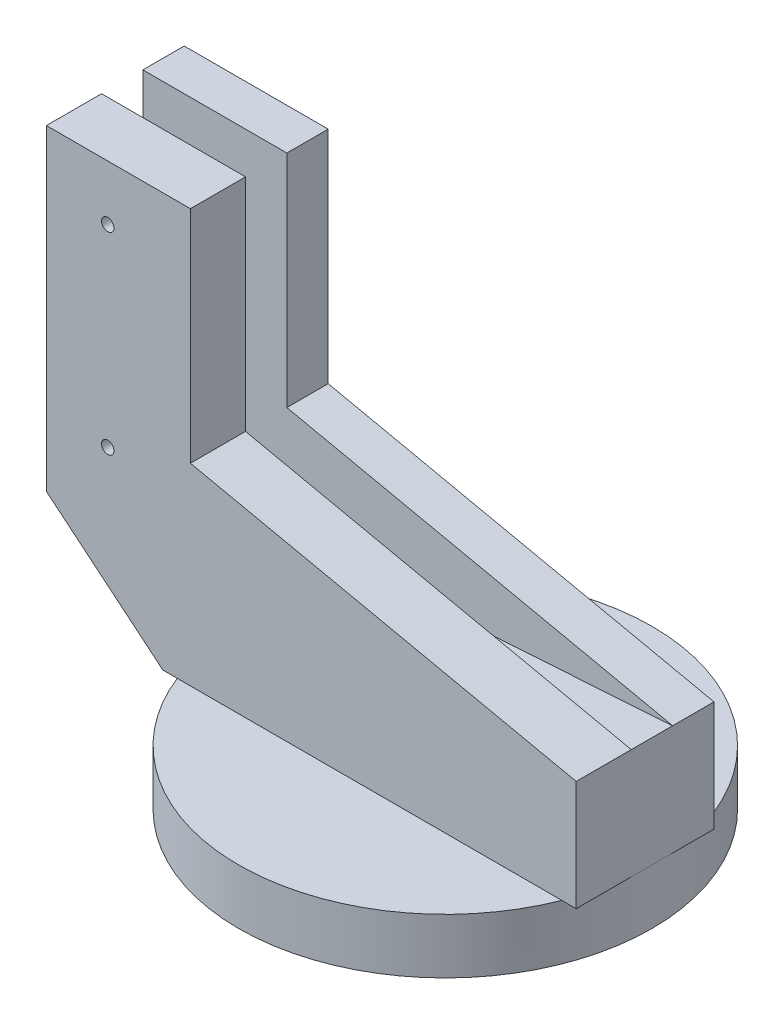
SolidWorks part; units mm, degrees
ref_plane "Front Plane" through (0, 0, 0) normal (0, 0, 1) x (1, 0, 0)
ref_plane "Top Plane" through (0, 0, 0) normal (0, 1, 0) x (1, 0, 0)
ref_plane "Right Plane" through (0, 0, 0) normal (1, 0, 0) x (0, 0, -1)
sketch "Sketch1" plane through (0, 0, 0) normal (0, 1, 0) x (1, 0, 0)
  circle A0 centre (0, 0) radius 75
  dimension "D1" = 150
extrude "Boss-Extrude1" add sketch "Sketch1" along normal blind 20
sketch "Sketch2" plane through (0, 0, 0) normal (0, 0, 1) x (1, 0, 0)
  line L0 (75, 20) -> (-75, 20) construction
  line L1 (75, 20) -> (-75, 20)
  line L2 (-95, 150) -> (-95, 80) construction
  line L3 (-75, 20) -> (-117.25, 55)
  line L4 (-117.25, 55) -> (-117.25, 170)
  line L5 (-117.25, 170) -> (-65, 170)
  line L6 (-65, 170) -> (-65, 90)
  line L7 (-65, 90) -> (75, 60)
  line L8 (75, 60) -> (75, 20)
  line L9 (-117.25, 55) -> (0, 55)
  line L10 (0, 55) -> (75, 60)
  circle A0 centre (-95, 150) radius 2.25
  circle A1 centre (-95, 80) radius 2.25
  dimension "D1" = 4.5
  dimension "D2" = 4.5
  dimension "D4" = 30
  dimension "D8" = 20
  dimension "D3" = 70
  dimension "D5" = 20
  dimension "D6" = 140
  dimension "D7" = 150
  dimension "D9" = 115
  dimension "D10" = 80
  dimension "D11" = 40
  dimension "D12" = 75
extrude "Boss-Extrude2" add sketch "Sketch2" against normal mid plane 15 contours L10 L9 L3 L1 L8 L7 region at (-9.1456, 38.7801, 0)
extrude "Boss-Extrude3" add sketch "Sketch2<4>" along normal blind 20 from surface contours L9 L10 L7 L6 L5 L4 A0 A1 | L10 L9 L3 L1 L8 L7 region at (-9.1456, 38.7801, 0) region at (-68.561, 98.8366, 0) starting at face at (-6.0357, 35.7143, 7.5)
sketch "Sketch2<4>" plane through (0, 0, 0) normal (0, 0, 1) x (1, 0, 0) same geometry as "Sketch2"
extrude "Boss-Extrude4" add sketch "Sketch2<5>" against normal blind 15 from surface contours L9 L10 L7 L6 L5 L4 A0 A1 | L10 L9 L3 L1 L8 L7 region at (-9.1456, 38.7801, 0) region at (-68.561, 98.8366, 0) starting at face at (-6.0357, 35.7143, -7.5)
sketch "Sketch2<5>" plane through (0, 0, 0) normal (0, 0, 1) x (1, 0, 0) same geometry as "Sketch2"
sketch "Sketch3" plane through (0, 0, 27.5) normal (0, 0, 1) x (1, 0, 0)
  line L0 (0, 55) -> (75, 60) construction
  line L1 (-117.25, 55) -> (0, 55) construction
  line L2 (0, 55) -> (75, 60)
  line L3 (-117.25, 55) -> (0, 55)
  line L8 (69.7764, 20) -> (75, 20)
  line L9 (75, 60) -> (-65, 90)
  line L10 (-65, 90) -> (-65, 170)
  line L11 (-65, 170) -> (-117.25, 170)
  line L12 (-117.25, 170) -> (-117.25, 55)
  line L13 (-117.25, 55) -> (-75, 20)
  line L14 (-75, 20) -> (-69.7764, 20)
  line L15 (-69.7764, 20) -> (69.7764, 20)
  line L17 (75, 60) -> (-65, 90)
  line L18 (-65, 90) -> (-65, 170)
  line L19 (-65, 170) -> (-117.25, 170)
  line L20 (-117.25, 170) -> (-117.25, 55)
  line L21 (-117.25, 55) -> (-75, 20)
  line L22 (-75, 20) -> (-69.7764, 20)
  line L23 (-69.7764, 20) -> (69.7764, 20)
  line L25 (69.7764, 20) -> (75, 20)
  line L26 (75, 20) -> (75, 60)
  line L27 (75, 20) -> (75, 60)
  circle A0 centre (-95, 150) radius 2.25 construction
  circle A1 centre (-95, 80) radius 2.25 construction
  circle A2 centre (-95, 150) radius 2.25
  circle A3 centre (-95, 80) radius 2.25
  dimension "D9" = 20
  dimension "D10" = 22.25
  dimension "D11" = 70
  dimension "D2" = 150
  dimension "D3" = 35
  dimension "D4" = 42.25
  dimension "D5" = 40
  dimension "D6" = 150
  dimension "D7" = 52.25
  dimension "D8" = 80
  dimension "D12" = 75
  dimension "D1" = 0
